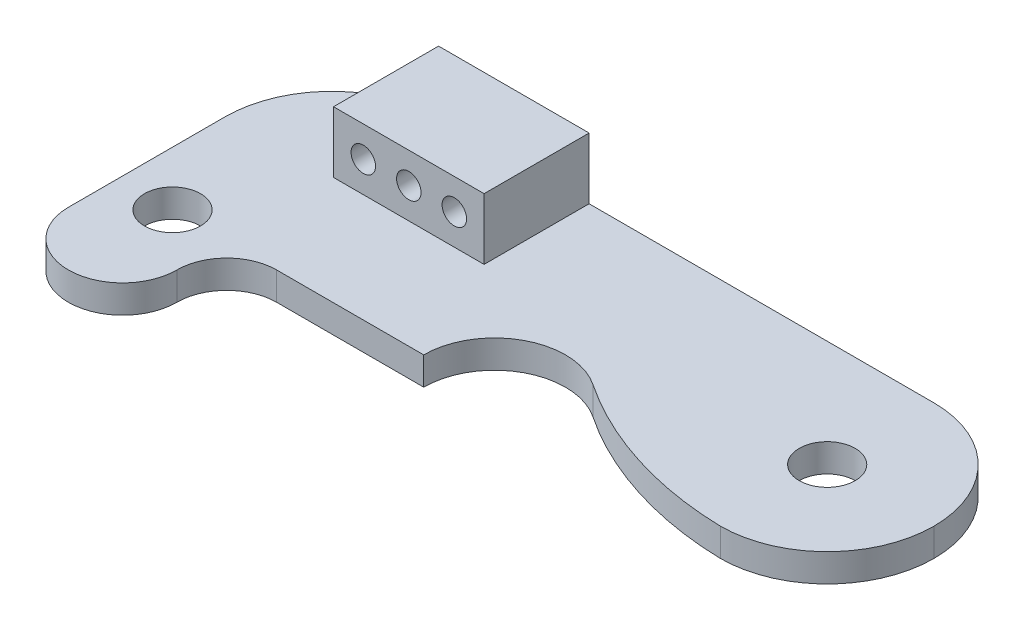
SolidWorks part; units mm, degrees
ref_plane "Front Plane" through (0, 0, 0) normal (0, 0, 1) x (1, 0, 0)
ref_plane "Top Plane" through (0, 0, 0) normal (0, 1, 0) x (1, 0, 0)
ref_plane "Right Plane" through (0, 0, 0) normal (1, 0, 0) x (0, 0, -1)
sketch "Sketch1" plane through (0, 0, 0) normal (0, 1, 0) x (1, 0, 0)
  line L15 (32.8531, -176.6025) -> (73.3531, -176.6025)
  line L17 (41.9031, -188.8025) -> (73.3531, -188.8025)
  line L21 (32.8531, -176.6025) -> (32.8531, -191.6525)
  line L22 (32.8531, -191.6525) -> (39.0531, -191.6525) construction
  line L24 (41.9031, -191.6525) -> (41.9031, -188.8025) construction
  line L28 (73.3531, -176.6025) -> (73.3531, -188.8025)
  arc A14 (41.9031, -188.8025) -> (39.0531, -191.6525) centre (41.9031, -191.6525) ccw
  arc A16 (32.8531, -191.6525) -> (39.0531, -191.6525) centre (35.9531, -191.6525) ccw
  point P8 (73.3531, -182.7025)
  dimension "D1" = 3.1
  dimension "D4" = 2.85
  dimension "D5" = 40.5
  dimension "D6" = 12.2
  dimension "D12" = 90
  dimension "D8" = 6.2
extrude "Boss-Extrude1" add sketch "Sketch1" along normal blind 1.6 contours L21 A16 A14 L17 L15 region at (51.9959, 0, 183.2694)
sketch "Sketch4" plane through (0, 1.6, 0) normal (0, 1, 0) x (1, 0, 0)
  line L0 (32.8531, -176.6025) -> (32.8531, -191.6525) construction
  line L1 (73.3531, -176.6025) -> (73.3531, -188.8025) construction
  line L2 (41.9031, -188.8025) -> (73.3531, -188.8025) construction
  line L3 (73.3531, -176.6025) -> (73.3531, -188.8025) construction
  line L4 (50.3031, -188.8025) -> (58.4031, -188.8025)
  line L6 (32.8531, -176.6025) -> (73.3531, -176.6025) construction
  circle A0 centre (67.2531, -182.7025) radius 1.6
  arc A1 (58.4031, -188.8025) -> (50.3031, -188.8025) centre (54.3531, -188.8025) ccw
  circle A2 centre (35.9531, -188.8025) radius 1.6
  dimension "D1" = 3.2
  dimension "D4" = 8.1
  dimension "D6" = 3.2
  dimension "D2" = 6.1
  dimension "D3" = 6.1
  dimension "D5" = 19
  dimension "D7" = 3.1
  dimension "D8" = 12.2
extrude "Cut-Extrude2" cut sketch "Sketch4" against normal through all
fillet "Fillet2" radius 6.1 3 edges at (73.3531, 0.8, 176.6025) (73.3531, 0.8, 188.8025) (32.8531, 0.8, 176.6025)
sketch "Sketch2" plane through (0, 1.6, 0) normal (0, 1, 0) x (1, 0, 0)
  line L0 (32.8531, -182.7025) -> (32.8531, -191.6525) construction
  line L1 (38.9531, -176.6025) -> (47.5531, -176.6025)
  line L2 (38.9531, -176.6025) -> (38.9531, -182.6025)
  line L3 (38.9531, -182.6025) -> (47.5531, -182.6025)
  line L4 (47.5531, -176.6025) -> (47.5531, -182.6025)
  dimension "D1" = 6
  dimension "D2" = 8.6
  dimension "D3" = 6.1
extrude "Boss-Extrude2" add sketch "Sketch2" along normal blind 3.5
sketch "Sketch3" plane through (0, 0, 176.6025) normal (0, 0, -1) x (-1, 0, 0)
  line L0 (-47.5531, 5.1) -> (-38.9531, 5.1) construction
  line L1 (-38.9531, 5.1) -> (-38.9531, 1.6) construction
  line L2 (-47.5531, 5.1) -> (-47.5531, 1.6) construction
  circle A0 centre (-45.8531, 3.35) radius 0.7
  circle A1 centre (-40.6531, 3.35) radius 0.7
  circle A2 centre (-43.2531, 3.35) radius 0.7
  dimension "D5" = 1.4
  dimension "D6" = 1.4
  dimension "D7" = 2.6
  dimension "D10" = 1.4
  dimension "D1" = 1.75
  dimension "D2" = 1.75
  dimension "D3" = 1.7
  dimension "D4" = 1.7
  dimension "D8" = 2.6
  dimension "D9" = 1.75
extrude "Cut-Extrude1" cut sketch "Sketch3" against normal up to next
fillet "Fillet1" radius 20 1 edges at (58.4031, 0.8, 188.8025)
